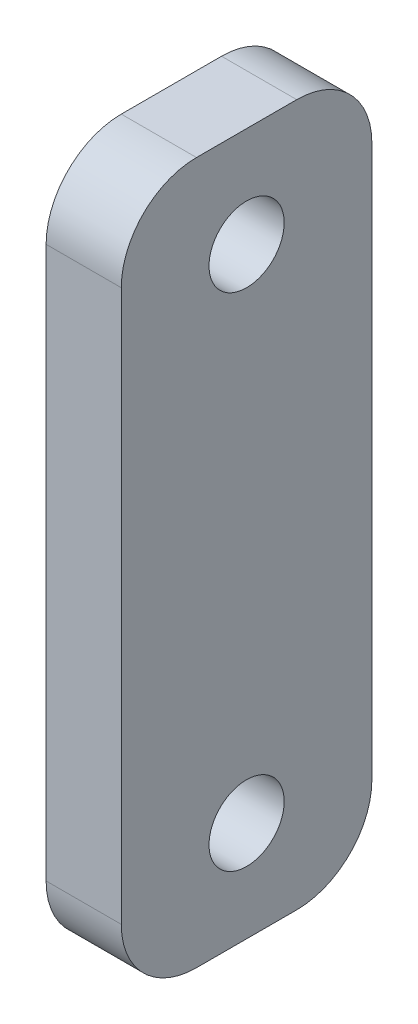
SolidWorks part; units mm, degrees
material "ABS"
ref_plane "Front Plane" through (0, 0, 0) normal (0, 0, 1) x (1, 0, 0)
ref_plane "Top Plane" through (0, 0, 0) normal (0, 1, 0) x (1, 0, 0)
ref_plane "Right Plane" through (0, 0, 0) normal (1, 0, 0) x (0, 0, -1)
sketch "Sketch1" plane through (0, 0, 0) normal (1, 0, 0) x (0, 0, -1)
  line L0 (0, 50) -> (0, -50) construction
  line L2 (-25, 70) -> (25, 70)
  line L3 (-25, 70) -> (-25, -70)
  line L4 (-25, -70) -> (25, -70)
  line L5 (25, 70) -> (25, -70)
  circle A0 centre (0, 50) radius 7.5
  circle A1 centre (0, -50) radius 7.5
  point P8 (0, 0)
  point P10 (-25, 0)
  point P11 (0, 70)
  point P12 (0, -70)
  dimension "D1" = 15
  dimension "D2" = 50
  dimension "D3" = 140
  dimension "D4" = 100
extrude "Boss-Extrude1" add sketch "Sketch1" along normal blind 15 contours L5 L2 L3 L4 A0 A1 | A0 | A1 region at (0, 0, 0) region at (0, 50, 0) region at (0, -50, 0)
extrude "Cut-Extrude1" cut sketch "Sketch1<3>" along normal through all contours A1 | A0 region at (0, -50, 0)
sketch "Sketch1<3>" plane through (0, 0, 0) normal (1, 0, 0) x (0, 0, -1) same geometry as "Sketch1"
fillet "Fillet1" radius 15 4 edges at (7.5, -70, -25) (7.5, -70, 25) (7.5, 70, -25) (7.5, 70, 25)
